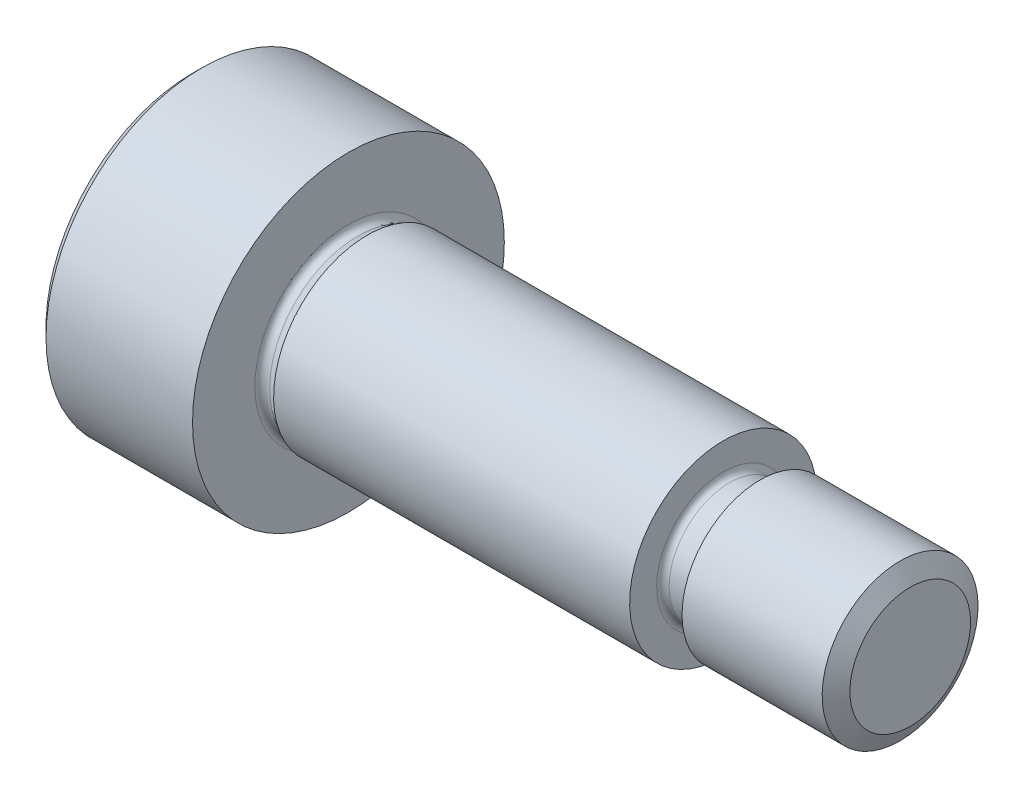
SolidWorks part; units mm, degrees
ref_plane "Front Plane" through (0, 0, 0) normal (0, 0, 1) x (1, 0, 0)
ref_plane "Top Plane" through (0, 0, 0) normal (0, 1, 0) x (1, 0, 0)
ref_plane "Right Plane" through (0, 0, 0) normal (1, 0, 0) x (0, 0, -1)
sketch "Sketch1" plane through (0, 0, 0) normal (0, 0, 1) x (1, 0, 0)
  line L0 (0, 0) -> (18.02, 0) construction
  line L1 (0, 0) -> (0, 6.6128) construction
  line L2 (0, 5) -> (-4.7, 5)
  line L3 (-4.7, 5) -> (-5, 4.7)
  line L4 (-5, 4.7) -> (-5, 1.8)
  line L5 (-4.7, 1.5) -> (-2.5, 1.5)
  line L6 (-2.5, 1.5) -> (-1.5987, 0)
  line L7 (0, 5) -> (0, 3)
  line L8 (13.1995, 2.5) -> (17.6935, 2.5)
  line L10 (12.873, 1.9345) -> (18.02, 1.9345)
  line L11 (18.02, 1.9345) -> (17.6935, 2.5)
  line L12 (18.02, 1.9345) -> (18.02, 0)
  line L13 (0, 0) -> (-1.5987, 0) construction
  line L15 (-5, 1.8) -> (-4.7, 1.5)
  line L16 (0.6, 3) -> (12.02, 3)
  line L17 (0.3, 2.8268) -> (0.6, 3)
  line L18 (13.1995, 2.5) -> (12.873, 1.9345)
  line L19 (12.873, 1.9345) -> (12.22, 1.9345)
  line L20 (12.02, 2.1345) -> (12.02, 3)
  arc A0 (0, 3) -> (0.3, 2.8268) centre (0.2, 3) ccw
  arc A1 (12.22, 1.9345) -> (12.02, 2.1345) centre (12.22, 2.1345) cw
  point P16 (0, 2.5)
  dimension "UnderheadRadius" = 0.2
  dimension "MajorDia" = 5
  dimension "D2" = 30
  dimension "ThreadMinorDia" = 3.869
  dimension "D4" = 60
  dimension "HeadHeight" = 5
  dimension "HeadDia" = 10
  dimension "D8" = 45
  dimension "D9" = 0.3
  dimension "SocketSize" = 3
  dimension "D12" = 59
  dimension "ThreadL" = 6
  dimension "SocketDepth" = 2.5
  dimension "ShoulderDiameter" = 6
  dimension "ShoulderLength" = 12.02
sketch "Sketch2" plane through (0, 0, 0) normal (0, 0, 1) x (1, 0, 0)
  line L0 (-4.7, 5) -> (-5, 4.7) construction
  line L1 (18.02, 1.9345) -> (18.02, 0) construction
  line L2 (0, 5) -> (-4.7, 5) construction
  line L3 (0, 5) -> (0, 3) construction
  line L4 (18.02, 1.9345) -> (17.6935, 2.5) construction
  line L5 (18.02, 1.9345) -> (17.6935, 2.5)
  line L6 (18.02, 1.9345) -> (18.02, 0)
  line L7 (0, 5) -> (0, 3)
  line L8 (0, 5) -> (-4.7, 5)
  line L9 (-4.7, 5) -> (-5, 4.7)
  line L12 (-1.5987, 0) -> (18.02, 0)
  line L13 (-2.5, 1.5) -> (-1.5987, 0) construction
  line L14 (-4.7, 1.5) -> (-2.5, 1.5) construction
  line L15 (-2.5, 1.5) -> (-1.5987, 0)
  line L16 (-4.7, 1.5) -> (-2.5, 1.5)
  line L17 (-5, 4.7) -> (-5, 1.8)
  line L18 (-5, 1.8) -> (-4.7, 1.5)
  line L19 (12.02, 2.1345) -> (12.02, 3)
  line L20 (0.6, 3) -> (12.02, 3)
  line L21 (12.22, 1.9345) -> (12.873, 1.9345)
  line L22 (12.873, 1.9345) -> (13.1995, 2.5)
  line L23 (13.1995, 2.5) -> (17.6935, 2.5)
  line L24 (0.3, 2.8268) -> (0.6, 3)
  arc A0 (0, 3) -> (0.3, 2.8268) centre (0.2, 3) ccw construction
  arc A1 (0, 3) -> (0.3, 2.8268) centre (0.2, 3) ccw
  arc A2 (12.02, 2.1345) -> (12.22, 1.9345) centre (12.22, 2.1345) ccw
revolve "ScrewRevolve" add sketch "Sketch2" angle 360 about L12
sketch "Sketch3" plane through (-5, 0, 0) normal (-1, 0, 0) x (0, 0, 1)
  line L1 (-0.866, 1.5) -> (-1.7321, 0)
  line L2 (-1.7321, 0) -> (-0.866, -1.5)
  line L3 (-0.866, -1.5) -> (0.866, -1.5)
  line L4 (0.866, -1.5) -> (1.7321, 0)
  line L5 (1.7321, 0) -> (0.866, 1.5)
  line L6 (0.866, 1.5) -> (-0.866, 1.5)
  circle A0 centre (0, 0) radius 1.5 construction
extrude "HexExtrude" cut sketch "Sketch3" against normal up to surface (2.3606 mm away)
